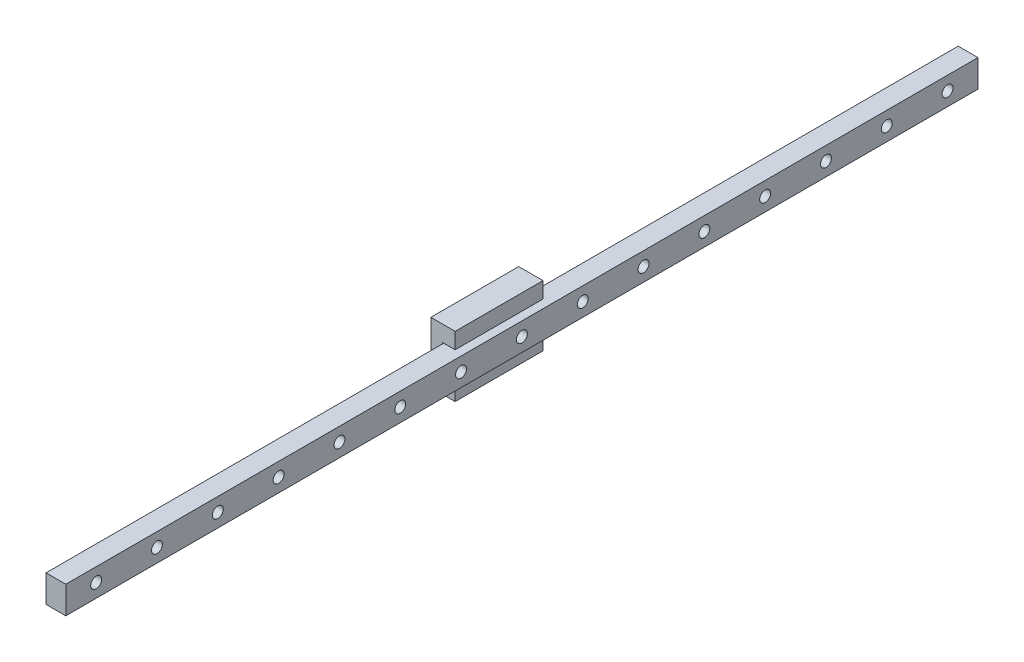
SolidWorks part; units mm, degrees
ref_plane "Front Plane" through (0, 0, 0) normal (0, 0, 1) x (1, 0, 0)
ref_plane "Top Plane" through (0, 0, 0) normal (0, 1, 0) x (1, 0, 0)
ref_plane "Right Plane" through (0, 0, 0) normal (1, 0, 0) x (0, 0, -1)
sketch "Sketch1" plane through (0, 0, 0) normal (0, 0, 1) x (1, 0, 0)
  line L1 (3.25, 4.5) -> (-3.25, 4.5)
  line L2 (3.25, 4.5) -> (3.25, -4.5)
  line L3 (3.25, -4.5) -> (-3.25, -4.5)
  line L4 (-3.25, 4.5) -> (-3.25, -4.5)
  line L5 (0, -4.5) -> (0, 4.5) construction
  line L6 (3.25, 0) -> (-3.25, 0) construction
  point P0 (0, 0)
  dimension "D1" = 6.5
  dimension "D2" = 9
extrude "Boss-Extrude1" add sketch "Sketch1" along normal mid plane 300
sketch "Sketch2" plane through (0, 0, 0) normal (0, 0, 1) x (1, 0, 0)
  line L0 (3.25, -4.5) -> (3.25, 4.5) construction
  line L1 (0.75, 10) -> (-7.25, 10)
  line L2 (0.75, 10) -> (0.75, -10)
  line L3 (0.75, -10) -> (-7.25, -10)
  line L4 (-7.25, 10) -> (-7.25, -10)
  line L5 (-3.25, -10) -> (-3.25, 10) construction
  line L6 (0.75, 0) -> (-7.25, 0) construction
  line L7 (0.75, 4.75) -> (-3.45, 4.75)
  line L8 (0.75, 4.75) -> (0.75, -4.75)
  line L9 (0.75, -4.75) -> (-3.45, -4.75)
  line L10 (-3.45, 4.75) -> (-3.45, -4.75)
  line L11 (-1.35, -4.75) -> (-1.35, 4.75) construction
  line L12 (0.75, 0) -> (-3.45, 0) construction
  line L13 (-3.25, 4.5) -> (-3.25, -4.5) construction
  point P144 (-1.35, 0)
  point P340 (-3.25, 0)
  dimension "D1" = 8
  dimension "D2" = 2.5
  dimension "D3" = 0.2
  dimension "D4" = 9.5
  dimension "D5" = 20
extrude "Boss-Extrude2" add sketch "Sketch2" along normal mid plane 28.9 separate body contours L10 L7 L2 L1 L4 L3 L9 region at (-3.8812, 0, 0)
hole_wizard "M3x0.5 Tapped Hole1" positions "Sketch3" profile "Sketch4" tap size "M3x0.5" standard "ANSI Metric"
sketch "Sketch3" plane through (-7.25, 0, 0) normal (-1, 0, 0) x (0, 0, 1)
  line L1 (-5, 7.5) -> (5, 7.5)
  line L2 (-5, 7.5) -> (-5, -7.5)
  line L3 (-5, -7.5) -> (5, -7.5)
  line L4 (5, 7.5) -> (5, -7.5)
  line L5 (0, -7.5) -> (0, 7.5) construction
  line L6 (-5, 0) -> (5, 0) construction
  point P5 (-5, 7.5)
  point P6 (5, -7.5)
  point P259 (-5, -7.5)
  point P260 (5, 7.5)
  dimension "D1" = 10
  dimension "D2" = 15
sketch "Sketch4" plane through (-7.25, 7.5, -5) normal (0, 1, 0) x (0, 0, 1)
  line L0 (0, 0) -> (0, 3.7511)
  line L1 (0, 3.7511) -> (1.25, 3)
  line L2 (1.25, 3) -> (1.25, 0)
  line L5 (1.25, 0) -> (0, 0)
  line L10 (0, 3.7511) -> (-1.25, 3) construction
  line L11 (0, -6.35) -> (0, 107.95) construction
  dimension "Tap Drill Dia." = 2.5
  dimension "Tap Drill Depth" = 3
  dimension "Drill Angle" = 118
hole_wizard "CBORE for M3 SHCS1" positions "Sketch5" profile "Sketch6" counterbore size "M3" standard "ANSI Metric" end condition through all
sketch "Sketch5" plane through (-3.25, 0, 0) normal (-1, 0, 0) x (0, 0, 1)
  line L0 (-150, 0) -> (-140, 0) construction
  line L1 (-150, 4.5) -> (-150, -4.5) construction
  point P0 (-140, 0)
  dimension "D1" = 10
sketch "Sketch6" plane through (-3.25, 0, -140) normal (0, 1, 0) x (0, 0, 1)
  line L0 (0, 0) -> (0, 6.5)
  line L1 (0, 6.5) -> (1.8, 6.5)
  line L3 (1.8, 6.5) -> (1.8, 3)
  line L4 (1.8, 3) -> (3.25, 3)
  line L5 (3.25, 3) -> (3.25, 0)
  line L7 (3.25, 0) -> (0, 0)
  line L11 (0, -6.35) -> (0, 107.95) construction
  dimension "Thru Hole Dia." = 3.6
  dimension "Thru Hole Depth" = 6.5
  dimension "C'Bore Dia." = 6.5
  dimension "C'Bore Depth" = 3
pattern_linear "LPattern1" count 15 spacing 20 along (0, 0, 1) of "CBORE for M3 SHCS1"
move or copy body "Body-Move/Copy1" bodies to move or copy 103 copy no translate (0, 0, 5)
